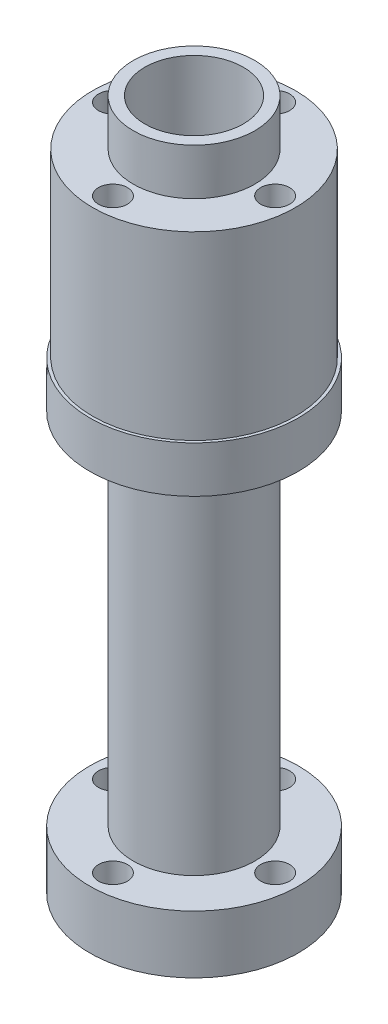
SolidWorks part; units mm, degrees
other "细节项目1"
other "细节项目2"
other "细节项目3"
material "6061-T6 (SS)"
ref_plane "前视基准面" through (0, 0, 0) normal (0, 0, 1) x (1, 0, 0)
ref_plane "上视基准面" through (0, 0, 0) normal (0, 1, 0) x (1, 0, 0)
ref_plane "右视基准面" through (0, 0, 0) normal (1, 0, 0) x (0, 0, -1)
sketch "草图1" plane through (0, 0, 0) normal (0, 0, 1) x (1, 0, 0)
  line L0 (0, 0) -> (0, 22.2724) construction
  line L1 (-9, 36) -> (-5.25, 36)
  line L2 (-4.25, 0) -> (-9, 0)
  line L3 (-4.25, 0) -> (-4.25, 55.6)
  line L4 (-4.25, 55.6) -> (-9, 55.6)
  line L5 (-9, 0) -> (-9, 5)
  line L6 (-5.25, 36) -> (-5.25, 5)
  line L7 (-5.25, 5) -> (-9, 5)
  line L8 (-9, 36) -> (-9, 55.6)
  dimension "D1" = 8.5
  dimension "D2" = 18
  dimension "D3" = 55.6
  dimension "D4" = 36
  dimension "D5" = 5
  dimension "D6" = 1
revolve "旋转1" add sketch "草图1" angle 360 about L0
sketch "草图2" plane through (0, 55.6, 0) normal (0, 1, 0) x (1, 0, 0)
  circle A0 centre (0, 0) radius 7 construction
  circle A1 centre (0, 7) radius 1.25
  circle A2 centre (0, -7) radius 1.25
  circle A3 centre (-7, 0) radius 1.25
  circle A4 centre (7, 0) radius 1.25
  dimension "D1" = 14
  dimension "D2" = 2.5
extrude "切除-拉伸1" cut sketch "草图2" against normal blind 10
cosmetic thread "装饰螺纹线3" parameters "D2"=3
cosmetic thread "装饰螺纹线4" parameters "D2"=3
cosmetic thread "装饰螺纹线5" parameters "D2"=3
cosmetic thread "装饰螺纹线6" parameters "D2"=3
extrude "切除-拉伸2" cut sketch "草图2<2>" along normal blind 6 from surface starting at face at (0, 0, -4.25)
sketch "草图2<2>" plane through (0, 55.6, 0) normal (0, 1, 0) x (1, 0, 0) same geometry as "草图2"
cosmetic thread "装饰螺纹线1" parameters "D2"=3
cosmetic thread "装饰螺纹线2" parameters "D2"=3
sketch "草图3" plane through (0, 55.6, 0) normal (0, 1, 0) x (1, 0, 0)
  circle A0 centre (0, 0) radius 8.75
  dimension "D1" = 17.5
extrude "切除-拉伸3" cut sketch "草图3" against normal offset from surface (15.6 mm away) 4 flip side to cut up to face at (0, 36, -5.25)
sketch "草图4" plane through (0, 55.6, 0) normal (0, 1, 0) x (1, 0, 0)
  circle A0 centre (0, 0) radius 5.25
  circle A1 centre (0, 0) radius 4.25 construction
  circle A2 centre (0, 0) radius 4.25
  dimension "D1" = 10.5
extrude "凸台-拉伸1" add sketch "草图4" along normal blind 4
